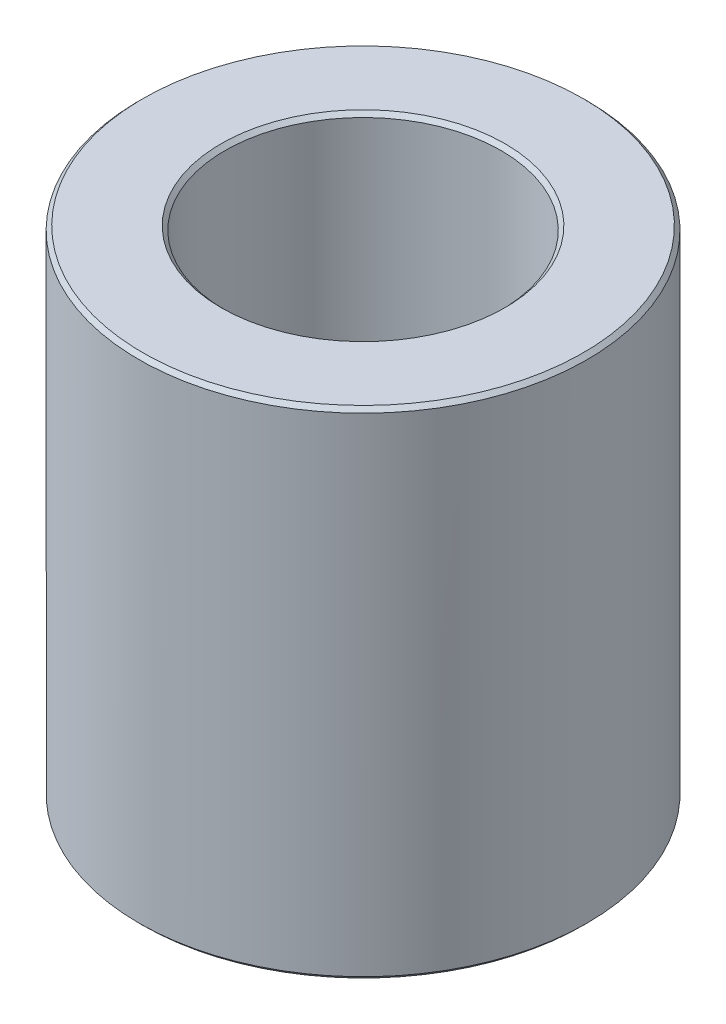
SolidWorks part; units mm, degrees
ref_plane "Front Plane" through (0, 0, 0) normal (0, 0, 1) x (1, 0, 0)
ref_plane "Top Plane" through (0, 0, 0) normal (0, 1, 0) x (1, 0, 0)
ref_plane "Right Plane" through (0, 0, 0) normal (1, 0, 0) x (0, 0, -1)
sketch "Sketch1" plane through (0, 0, 0) normal (0, 1, 0) x (1, 0, 0)
  circle A0 centre (0, 0) radius 47.5
  dimension "SLEEVE_OD" = 95
extrude "Boss-Extrude1" add sketch "Sketch1" along normal blind 105.1038
sketch "Sketch2" plane through (0, 0, 0) normal (0, 1, 0) x (1, 0, 0)
  circle A0 centre (0, 0) radius 29.2661
  dimension "BORE_D" = 58.5322
extrude "Cut-Extrude1" cut sketch "Sketch2" along normal through all
chamfer "Chamfer1" distance 0.8368 angle 45 4 edges at (0, 105.1038, 29.2661) (0, 0, 29.2661) (0, 0, 47.5) (0, 105.1038, 47.5)
